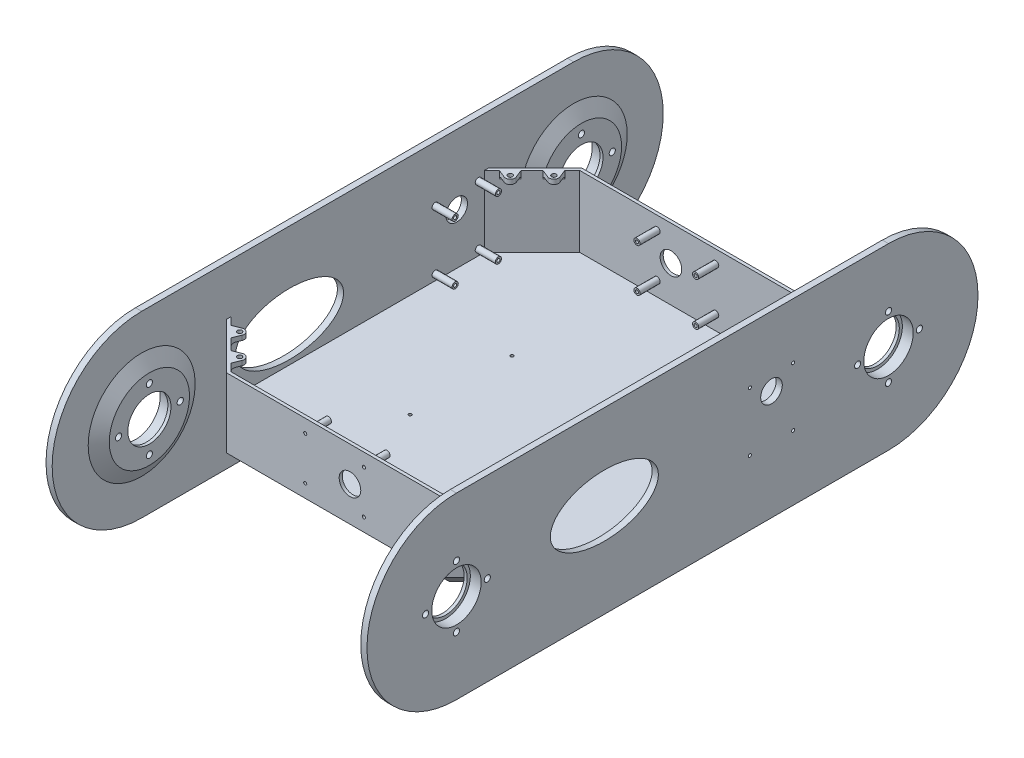
SolidWorks part; units mm, degrees
material "Zoltek Panex 33"
ref_plane "Front Plane" through (0, 0, 0) normal (0, 0, 1) x (1, 0, 0)
ref_plane "Top Plane" through (0, 0, 0) normal (0, 1, 0) x (1, 0, 0)
ref_plane "Right Plane" through (0, 0, 0) normal (1, 0, 0) x (0, 0, -1)
sketch "Sketch1" plane through (0, 0, 0) normal (0, 1, 0) x (1, 0, 0)
  line L1 (-100, -115) -> (100, -115)
  line L2 (-100, -115) -> (-100, 115)
  line L3 (-100, 115) -> (100, 115)
  line L4 (100, -115) -> (100, 115)
  line L5 (-100, -115) -> (100, 115) construction
  line L6 (-100, 115) -> (100, -115) construction
  point P0 (0, 0)
  dimension "D1" = 200
  dimension "D2" = 230
extrude "Boss-Extrude1" add sketch "Sketch1" along normal blind 52 contours L3 L4 L1 L2
chamfer "Chamfer1" distance 30 angle 45 4 edges at (-100, 26, -115) (100, 26, -115) (-100, 26, 115) (100, 26, 115)
sketch "Sketch2" plane through (100, 0, 0) normal (1, 0, 0) x (0, 0, -1)
  line L0 (115, 26) -> (-115, 26) construction
  line L1 (115, 52) -> (115, 0) construction
  line L2 (-115, 52) -> (-115, 0) construction
  line L3 (-140, 26) -> (140, 26) construction
  line L4 (-140, 84) -> (140, 84)
  line L5 (-140, -32) -> (140, -32)
  arc A0 (-140, 84) -> (-140, -32) centre (-140, 26) ccw
  arc A1 (140, -32) -> (140, 84) centre (140, 26) ccw
  point P8 (0, 26)
  dimension "D2" = 58
  dimension "D1" = 280
extrude "Boss-Extrude2" add sketch "Sketch2" along normal blind 4
ref_plane "Plane1" through (95, 0, 0) normal (-1, 0, 0) x (0, 0, 1)
sketch "Sketch3" plane through (95, 0, 0) normal (-1, 0, 0) x (0, 0, 1)
  circle A0 centre (140, 26) radius 16
  circle A1 centre (140, 26) radius 26
  dimension "D1" = 32
  dimension "D2" = 52
extrude "Boss-Extrude3" add sketch "Sketch3" against normal up to surface (5 mm away) draft 60 contours A1 up to face at (100, 26, 0) draft outward yes
sketch "Sketch4" plane through (95, 0, 0) normal (-1, 0, 0) x (0, 0, 1)
  circle A0 centre (140, 26) radius 14
  dimension "D1" = 28
extrude "Cut-Extrude1" cut sketch "Sketch4" against normal blind 2
sketch "Sketch5" plane through (97, 0, 0) normal (-1, 0, 0) x (0, 0, 1)
  circle A0 centre (140, 26) radius 16
  dimension "D1" = 32
extrude "Cut-Extrude2" cut sketch "Sketch5" against normal through all
mirror "Mirror1" about plane through (0, 0, 0) normal (0, 0, 1) of "Cut-Extrude2", "Cut-Extrude1", "Boss-Extrude3"
mirror "Mirror2" about plane through (0, 0, 0) normal (1, 0, 0) of "Mirror1", "Cut-Extrude2", "Cut-Extrude1", "Boss-Extrude3", "Boss-Extrude2"
sketch "Sketch6" plane through (-95, 0, 0) normal (1, 0, 0) x (0, 0, -1)
  line L0 (-140, 26) -> (-140, 46) construction
  circle A0 centre (-140, 26) radius 16 construction
  circle A1 centre (-140, 26) radius 16 construction
  circle A2 centre (-140, 46) radius 2
  circle A3 centre (-120, 26) radius 2
  circle A4 centre (-140, 6) radius 2
  circle A5 centre (-160, 26) radius 2
  point P13 (-140, 26)
  dimension "D1" = 4
  dimension "D2" = 20
  dimension "D3" = 4
extrude "Cut-Extrude3" cut sketch "Sketch6" against normal through all and the other way through all
mirror "Mirror3" about plane through (0, 0, 0) normal (0, 0, 1) of "Cut-Extrude3"
sketch "Sketch7" plane through (0, 52, 0) normal (0, 1, 0) x (1, 0, 0)
  line L0 (-100, 82.1716) -> (-69.1716, 113)
  line L1 (-100, 140) -> (-100, -140) construction
  line L2 (-69.1716, 113) -> (69.1716, 113)
  line L3 (0, 113) -> (0, 0) construction
  line L4 (0, 0) -> (-100, 0) construction
  line L5 (-70, 115) -> (-100, 85) construction
  line L6 (-70, 115) -> (70, 115) construction
  line L7 (-100, -82.1716) -> (-69.1716, -113)
  line L8 (-69.1716, -113) -> (69.1716, -113)
  line L9 (100, -82.1716) -> (69.1716, -113)
  line L10 (100, 82.1716) -> (69.1716, 113)
  line L11 (-100, -85) -> (-100, 85) construction
  line L12 (-100, -82.1716) -> (-100, 82.1716)
  line L13 (100, 140) -> (100, -140) construction
  line L14 (100, 82.1716) -> (100, -82.1716)
  point P16 (0, -113)
  dimension "D1" = 2
  dimension "D2" = 2
extrude "Cut-Extrude4" cut sketch "Sketch7" against normal blind 46 contours L0 L2 L10 L14 L9 L8 L7 L12
sketch "Sketch8" plane through (104, 0, 0) normal (1, 0, 0) x (0, 0, -1)
  line L0 (0, -32) -> (0, 84) construction
  line L1 (-140, -32) -> (140, -32) construction
  line L2 (140, 84) -> (-140, 84) construction
  line L3 (82.1716, 6) -> (82.1716, 52) construction
  line L4 (-82.1716, 6) -> (-82.1716, 52) construction
  line L5 (82.1716, 6) -> (82.1716, 52) construction
  line L6 (-82.1716, 6) -> (-82.1716, 52) construction
  line L7 (82.1716, 29) -> (-82.1716, 29) construction
  line L9 (78.1716, 10) -> (50.1716, 10) construction
  line L10 (78.1716, 10) -> (78.1716, 48) construction
  line L11 (78.1716, 48) -> (50.1716, 48) construction
  line L12 (50.1716, 10) -> (50.1716, 48) construction
  line L13 (78.1716, 10) -> (50.1716, 48) construction
  line L14 (78.1716, 48) -> (50.1716, 10) construction
  circle A0 centre (50.1716, 48) radius 1
  circle A1 centre (78.1716, 48) radius 1
  circle A2 centre (78.1716, 10) radius 1
  circle A3 centre (50.1716, 10) radius 1
  circle A4 centre (64.1716, 39) radius 7
  ellipse E0 centre (-44.1716, 29) end of major axis (-79.1716, 29) minor radius 20
  point P25 (64.1716, 48)
  point P37 (64.1716, 29)
  dimension "D7" = 2
  dimension "D8" = 14
  dimension "D1" = 20
  dimension "D2" = 35
  dimension "D3" = 3
  dimension "D4" = 38
  dimension "D5" = 28
  dimension "D6" = 4
  dimension "D9" = 9
extrude "Cut-Extrude5" cut sketch "Sketch8" against normal through all
chamfer "Chamfer3" distance 7 angle 45 6 edges at (-85, 0, -100) (85, 0, -100) (0, 0, -115) (85, 0, 100) (-85, 0, 100) (0, 0, 115)
sketch "Sketch9" plane through (0, 6, 0) normal (0, 1, 0) x (1, 0, 0)
  line L1 (-33, -33) -> (33, -33) construction
  line L2 (-33, -33) -> (-33, 33) construction
  line L3 (-33, 33) -> (33, 33) construction
  line L4 (33, -33) -> (33, 33) construction
  line L5 (-33, -33) -> (33, 33) construction
  line L6 (-33, 33) -> (33, -33) construction
  circle A0 centre (-33, 33) radius 1
  circle A1 centre (33, 33) radius 1
  circle A2 centre (33, -33) radius 1
  circle A3 centre (-33, -33) radius 1
  point P0 (0, 0)
  dimension "D3" = 2
  dimension "D1" = 66
  dimension "D2" = 66
extrude "Cut-Extrude6" cut sketch "Sketch9" against normal through all
sketch "Sketch10" plane through (0, 0, -115) normal (0, 0, -1) x (-1, 0, 0)
  line L0 (70, 29.5) -> (34.3735, 29.5) construction
  line L1 (-19, 15.5) -> (19, 15.5) construction
  line L2 (-19, 15.5) -> (-19, 43.5) construction
  line L3 (-19, 43.5) -> (19, 43.5) construction
  line L4 (19, 15.5) -> (19, 43.5) construction
  line L5 (-19, 15.5) -> (19, 43.5) construction
  line L6 (-19, 43.5) -> (19, 15.5) construction
  line L7 (70, 7) -> (70, 52) construction
  circle A0 centre (-19, 43.5) radius 1
  circle A1 centre (19, 43.5) radius 1
  circle A2 centre (19, 15.5) radius 1
  circle A3 centre (-19, 15.5) radius 1
  point P0 (0, 29.5)
  dimension "D3" = 2
  dimension "D1" = 38
  dimension "D2" = 28
extrude "Cut-Extrude7" cut sketch "Sketch10" against normal through all
sketch "Sketch11" plane through (100, 0, 0) normal (-1, 0, 0) x (0, 0, 1)
  circle A0 centre (-78.1716, 48) radius 2
  circle A1 centre (-50.1716, 48) radius 2
  circle A2 centre (-50.1716, 10) radius 2
  circle A3 centre (-78.1716, 10) radius 2
  circle A4 centre (-78.1716, 10) radius 1 construction
  circle A5 centre (-50.1716, 10) radius 1 construction
  circle A6 centre (-50.1716, 48) radius 1 construction
  circle A7 centre (-78.1716, 48) radius 1 construction
  circle A8 centre (-78.1716, 10) radius 1
  circle A9 centre (-50.1716, 10) radius 1
  circle A10 centre (-50.1716, 48) radius 1
  circle A11 centre (-78.1716, 48) radius 1
  dimension "D1" = 4
extrude "Boss-Extrude4" add sketch "Sketch11" along normal blind 13
mirror "Mirror4" about plane through (0, 0, 0) normal (1, 0, 0) of "Boss-Extrude4"
sketch "Sketch12" plane through (0, 0, -113) normal (0, 0, 1) x (1, 0, 0)
  circle A0 centre (-19, 43.5) radius 2
  circle A1 centre (19, 43.5) radius 2
  circle A2 centre (19, 15.5) radius 2
  circle A3 centre (-19, 15.5) radius 2
  circle A4 centre (-19, 15.5) radius 1 construction
  circle A5 centre (19, 15.5) radius 1 construction
  circle A6 centre (19, 43.5) radius 1 construction
  circle A7 centre (-19, 43.5) radius 1 construction
  circle A8 centre (-19, 15.5) radius 1
  circle A9 centre (19, 15.5) radius 1
  circle A10 centre (19, 43.5) radius 1
  circle A11 centre (-19, 43.5) radius 1
  dimension "D1" = 4
extrude "Boss-Extrude5" add sketch "Sketch12" along normal blind 13
mirror "Mirror5" about plane through (0, 0, 0) normal (0, 0, 1) of "Boss-Extrude5"
sketch "Sketch13" plane through (0, 0, 115) normal (0, 0, 1) x (1, 0, 0)
  line L0 (19, 43.5) -> (19, 15.5) construction
  line L1 (19, 29.5) -> (10, 29.5) construction
  circle A0 centre (10, 29.5) radius 7
  dimension "D1" = 14
  dimension "D2" = 9
extrude "Cut-Extrude8" cut sketch "Sketch13" against normal blind 3
sketch "Sketch14" plane through (0, 0, -115) normal (0, 0, -1) x (-1, 0, 0)
  line L0 (19, 43.5) -> (19, 15.5) construction
  line L1 (19, 29.5) -> (10, 29.5) construction
  circle A0 centre (10, 29.5) radius 7
  dimension "D1" = 14
  dimension "D2" = 9
extrude "Cut-Extrude9" cut sketch "Sketch14" against normal blind 3
sketch "Sketch15" plane through (0, 52, 0) normal (0, 1, 0) x (1, 0, 0)
  line L0 (-100, 76.5147) -> (-63.5147, 113) construction
  line L1 (-100, -82.1716) -> (-100, 82.1716) construction
  line L2 (-69.1716, 113) -> (69.1716, 113) construction
  line L3 (-100, 82.1716) -> (-69.1716, 113) construction
  line L4 (-81.7574, 94.7574) -> (-48.3087, 61.3087) construction
  line L5 (-100, 82.1716) -> (-69.1716, 113) construction
  line L6 (-95.1924, 86.9792) -> (-89.9327, 84.8969)
  line L7 (-88.8284, 87.6863) -> (-91.6569, 90.5147) construction
  line L8 (-88.1213, 94.0503) -> (-86.0391, 88.7906)
  line L9 (-73.9792, 108.1924) -> (-71.8969, 102.9327)
  line L10 (-81.0503, 101.1213) -> (-75.7906, 99.0391)
  line L11 (-95.1924, 86.9792) -> (-88.1213, 94.0503)
  line L12 (-81.0503, 101.1213) -> (-73.9792, 108.1924)
  line L13 (0, 0) -> (0, 117.5947) construction
  line L14 (-89.6858, 0) -> (89.6858, 0) construction
  line L15 (81.0503, 101.1213) -> (73.9792, 108.1924)
  line L16 (73.9792, 108.1924) -> (71.8969, 102.9327)
  line L17 (81.0503, 101.1213) -> (75.7906, 99.0391)
  line L18 (95.1924, 86.9792) -> (89.9327, 84.8969)
  line L19 (88.1213, 94.0503) -> (86.0391, 88.7906)
  line L20 (95.1924, 86.9792) -> (88.1213, 94.0503)
  line L21 (95.1924, -86.9792) -> (88.1213, -94.0503)
  line L22 (88.1213, -94.0503) -> (86.0391, -88.7906)
  line L23 (95.1924, -86.9792) -> (89.9327, -84.8969)
  line L24 (81.0503, -101.1213) -> (75.7906, -99.0391)
  line L25 (73.9792, -108.1924) -> (71.8969, -102.9327)
  line L26 (81.0503, -101.1213) -> (73.9792, -108.1924)
  line L27 (-81.0503, -101.1213) -> (-73.9792, -108.1924)
  line L28 (-73.9792, -108.1924) -> (-71.8969, -102.9327)
  line L29 (-81.0503, -101.1213) -> (-75.7906, -99.0391)
  line L30 (-95.1924, -86.9792) -> (-89.9327, -84.8969)
  line L31 (-88.1213, -94.0503) -> (-86.0391, -88.7906)
  line L32 (-95.1924, -86.9792) -> (-88.1213, -94.0503)
  circle A0 centre (-88.8284, 87.6863) radius 1.5
  circle A1 centre (-74.6863, 101.8284) radius 1.5
  arc A2 (-89.9327, 84.8969) -> (-86.0391, 88.7906) centre (-88.8284, 87.6863) ccw
  arc A3 (-71.8969, 102.9327) -> (-75.7906, 99.0391) centre (-74.6863, 101.8284) cw
  circle A4 centre (74.6863, 101.8284) radius 1.5
  arc A5 (71.8969, 102.9327) -> (75.7906, 99.0391) centre (74.6863, 101.8284) ccw
  circle A6 centre (88.8284, 87.6863) radius 1.5
  arc A7 (89.9327, 84.8969) -> (86.0391, 88.7906) centre (88.8284, 87.6863) cw
  circle A8 centre (88.8284, -87.6863) radius 1.5
  arc A9 (89.9327, -84.8969) -> (86.0391, -88.7906) centre (88.8284, -87.6863) ccw
  circle A10 centre (74.6863, -101.8284) radius 1.5
  arc A11 (71.8969, -102.9327) -> (75.7906, -99.0391) centre (74.6863, -101.8284) cw
  circle A12 centre (-74.6863, -101.8284) radius 1.5
  arc A13 (-71.8969, -102.9327) -> (-75.7906, -99.0391) centre (-74.6863, -101.8284) ccw
  circle A14 centre (-88.8284, -87.6863) radius 1.5
  arc A15 (-89.9327, -84.8969) -> (-86.0391, -88.7906) centre (-88.8284, -87.6863) cw
  dimension "D1" = 4
  dimension "D2" = 3
  dimension "D3" = 6
  dimension "D4" = 10
  dimension "D5" = 10
extrude "Boss-Extrude6" add sketch "Sketch15" against normal blind 3
fillet "Fillet1" radius 2 8 edges at (-91.6569, 49, 90.5147) (-77.5147, 49, 104.6569) (91.6569, 49, 90.5147) (77.5147, 49, 104.6569) (91.6569, 49, -90.5147) (77.5147, 49, -104.6569) (-91.6569, 49, -90.5147) (-77.5147, 49, -104.6569)
